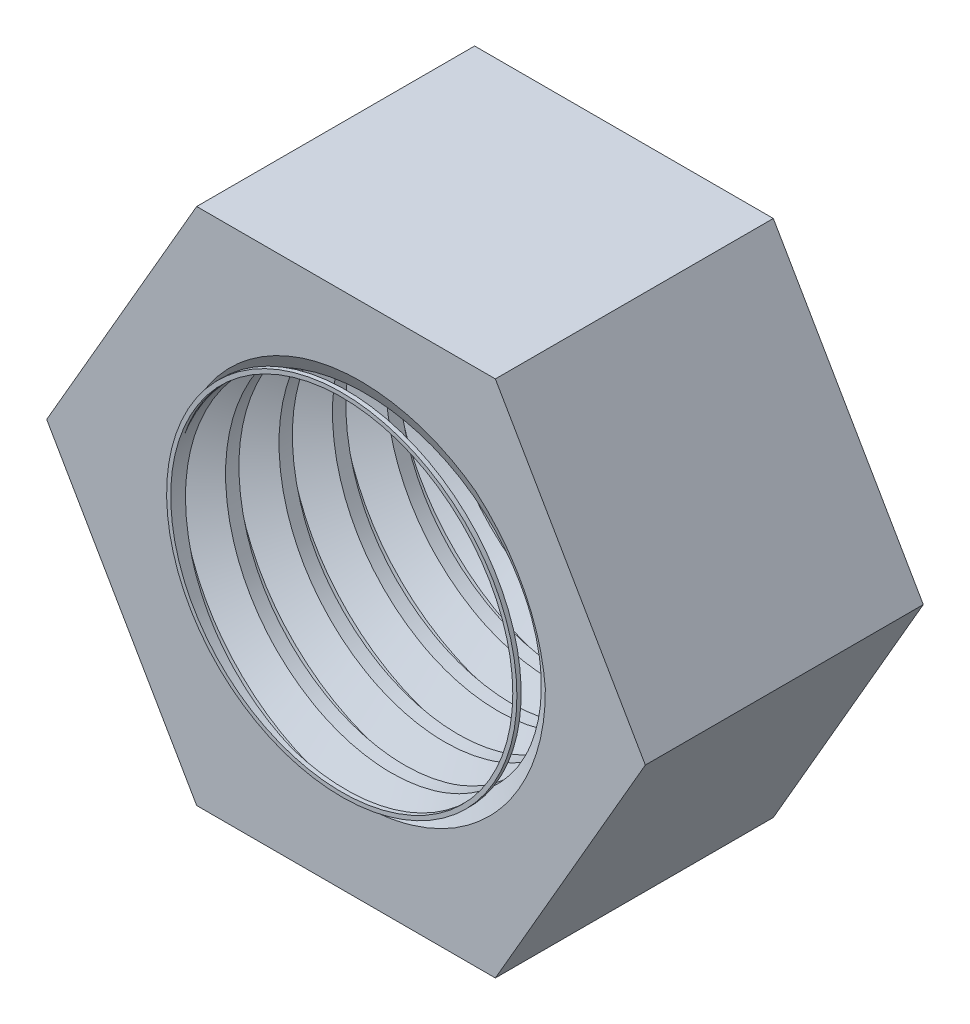
SolidWorks part; units mm, degrees
ref_plane "Front Plane" through (0, 0, 0) normal (0, 0, 1) x (1, 0, 0)
ref_plane "Top Plane" through (0, 0, 0) normal (0, 1, 0) x (1, 0, 0)
ref_plane "Right Plane" through (0, 0, 0) normal (1, 0, 0) x (0, 0, -1)
sketch "Sketch1" plane through (0, 0, 0) normal (0, 0, 1) x (1, 0, 0)
  circle A0 centre (0, 0) radius 7
  dimension "D1" = 14
extrude "Boss-Extrude1" add sketch "Sketch1" along normal blind 6.5
sketch "Sketch14" plane through (0, 0, 6.5) normal (0, 0, 1) x (1, 0, 0)
  line L0 (-7, 0) -> (7, 0) construction
  line L1 (-3.4924, -6.0665) -> (3.4924, -6.0665)
  line L2 (-3.4924, 6.0665) -> (3.4924, 6.0665)
  line L3 (-3.4924, 6.0665) -> (-7, 0)
  line L4 (-7, 0) -> (-3.4924, -6.0665)
  line L5 (3.4924, 6.0665) -> (7, 0)
  line L6 (3.4924, -6.0665) -> (7, 0)
  circle A0 centre (0, 0) radius 7 construction
  circle A1 centre (0, 0) radius 7
  circle A2 centre (0, 0) radius 4
  circle M10 centre (0, 0) radius 7
  dimension "D1" = 6.9848
extrude "Cut-Extrude1" cut sketch "Sketch14" against normal blind 6.5 contours L2 M10 | L5 M10 | L6 M10 | L1 M10 | L4 M10 | L3 M10 | L0 A2 | A2 L0 region at (0, -1.6977, 6.5) region at (0, 1.6977, 6.5) region at (5.5737, -3.2226, 6.5) region at (5.5737, 3.2226, 6.5) region at (0, 6.4421, 6.5) region at (0, -6.4421, 6.5) region at (-5.5737, 3.2226, 6.5) region at (-5.5737, -3.2226, 6.5)
thread "Thread2" pitch 1.25 method cut profile "Thread Profile2" start angle 0, offset 1, length 0, pitch 1.25, diameter 8
ref_plane "Plane2" through (-4, 0, 7.5) normal (0, -1, 0) x (-1, 0, 0)
sketch "Thread Profile2" plane through (-4, 0, 7.5) normal (0, -1, 0) x (-1, 0, 0)
  line L0 (0, 0) -> (0, 1.25) construction
  line L1 (0, 0) -> (0.6766, 0.3906)
  line L2 (0.6766, 0.3906) -> (0.6766, 0.5469)
  line L3 (0.6766, 0.5469) -> (0, 0.9375)
  line L4 (0.6766, 0.4687) -> (0, 0.4687) construction
  line L11 (0, 0) -> (0, 0.9375)
  point P2 (0, 0)
  dimension "Pitch" = 1.25
  dimension "Profile_Angle" = 60
  dimension "Profile_Land" = 0.1562
  dimension "Profile_Height" = 0.6766
sketch "Sketch17" plane through (0, 0, 6.5) normal (0, 0, 1) x (1, 0, 0)
  circle A0 centre (0, 0) radius 4
  circle A1 centre (0, 0) radius 4.0959
extrude "Boss-Extrude2" add sketch "Sketch17" along normal blind 0.1
ref_axis "Axis1" through (0, 0, 0) along (0, 0, 1)
